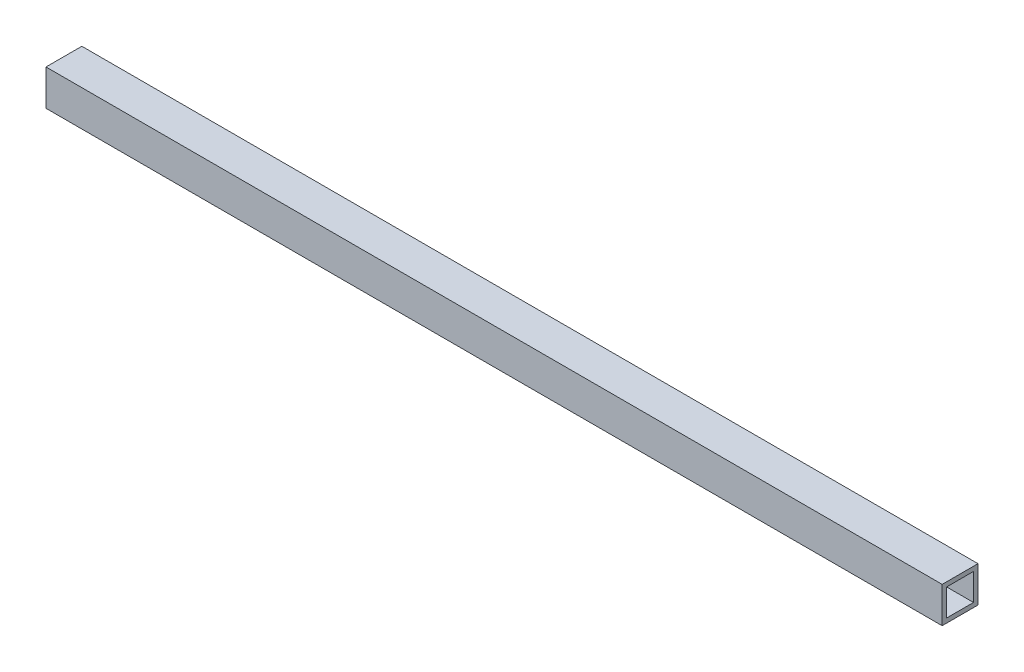
SolidWorks part; units mm, degrees
ref_plane "Front Plane" through (0, 0, 0) normal (0, 0, 1) x (1, 0, 0)
ref_plane "Top Plane" through (0, 0, 0) normal (0, 1, 0) x (1, 0, 0)
ref_plane "Right Plane" through (0, 0, 0) normal (1, 0, 0) x (0, 0, -1)
sketch "Sketch1" plane through (0, 0, 0) normal (1, 0, 0) x (0, 0, -1)
  line L1 (0, 0) -> (19.05, 0)
  line L2 (0, 0) -> (0, 19.05)
  line L3 (0, 19.05) -> (19.05, 19.05)
  line L4 (19.05, 0) -> (19.05, 19.05)
  dimension "D1" = 19.05
  dimension "D2" = 19.05
extrude "Extrude-Thin1" add sketch "Sketch1" along normal blind 635 thin thin type one direction wall 3.175
